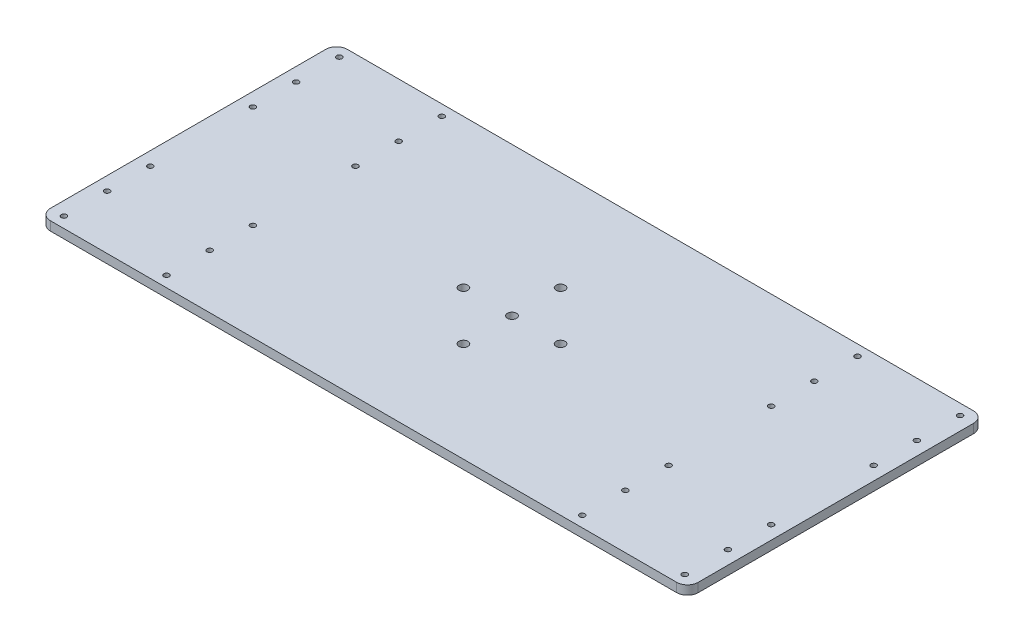
SolidWorks part; units mm, degrees
ref_plane "Front Plane" through (0, 0, 0) normal (0, 0, 1) x (1, 0, 0)
ref_plane "Top Plane" through (0, 0, 0) normal (0, 1, 0) x (1, 0, 0)
ref_plane "Right Plane" through (0, 0, 0) normal (1, 0, 0) x (0, 0, -1)
sketch "Sketch1" plane through (0, 0, 0) normal (0, 1, 0) x (1, 0, 0)
  line L0 (-172.5, 82.5) -> (-172.5, -82.5) construction
  line L1 (-174, -82.5) -> (174, -82.5)
  line L2 (-180, -76.5) -> (-180, 76.5)
  line L3 (-174, 82.5) -> (174, 82.5)
  line L4 (180, -76.5) -> (180, 76.5)
  line L5 (-180, -82.5) -> (180, 82.5) construction
  line L6 (-180, 82.5) -> (180, -82.5) construction
  line L7 (0, 0) -> (-30, -30) construction
  line L8 (0, 82.5) -> (0, -82.5) construction
  line L9 (-180, 0) -> (180, 0) construction
  line L10 (-9.5, -10) -> (9.5, -10) construction
  line L11 (-10, -9.5) -> (-10, 9.5) construction
  line L12 (-9.5, 10) -> (9.5, 10) construction
  line L13 (10, -9.5) -> (10, 9.5) construction
  line L14 (-10, -10) -> (10, 10) construction
  line L15 (-10, 10) -> (10, -10) construction
  circle A0 centre (-172.5, 76.5) radius 1.5
  circle A1 centre (-172.5, 52.5) radius 1.5
  circle A2 centre (-172.5, 28.5) radius 1.5
  circle A3 centre (-115.5, 76.5) radius 1.5
  circle A4 centre (-115.5, 52.5) radius 1.5
  circle A5 centre (-115.5, 28.5) radius 1.5
  circle A6 centre (115.5, 28.5) radius 1.5
  circle A7 centre (115.5, 52.5) radius 1.5
  circle A8 centre (115.5, 76.5) radius 1.5
  circle A9 centre (172.5, 28.5) radius 1.5
  circle A10 centre (172.5, 52.5) radius 1.5
  circle A11 centre (172.5, 76.5) radius 1.5
  circle A12 centre (172.5, -76.5) radius 1.5
  circle A13 centre (172.5, -52.5) radius 1.5
  circle A14 centre (172.5, -28.5) radius 1.5
  circle A15 centre (115.5, -76.5) radius 1.5
  circle A16 centre (115.5, -52.5) radius 1.5
  circle A17 centre (115.5, -28.5) radius 1.5
  circle A18 centre (-115.5, -28.5) radius 1.5
  circle A19 centre (-115.5, -52.5) radius 1.5
  circle A20 centre (-115.5, -76.5) radius 1.5
  circle A21 centre (-172.5, -28.5) radius 1.5
  circle A22 centre (-172.5, -52.5) radius 1.5
  circle A23 centre (-172.5, -76.5) radius 1.5
  arc A24 (9.5, 10) -> (10, 9.5) centre (9.5, 9.5) cw construction
  arc A25 (10, -9.5) -> (9.5, -10) centre (9.5, -9.5) cw construction
  arc A26 (-9.5, -10) -> (-10, -9.5) centre (-9.5, -9.5) cw construction
  arc A27 (-10, 9.5) -> (-9.5, 10) centre (-9.5, 9.5) cw construction
  circle A28 centre (0, 27) radius 2.5
  circle A29 centre (27, 0) radius 2.5
  circle A30 centre (0, -27) radius 2.5
  circle A31 centre (-27, 0) radius 2.5
  circle A32 centre (0, 0) radius 2.5
  circle A33 centre (-30, -30) radius 2.5 construction
  circle A34 centre (-30, 30) radius 2.5 construction
  circle A35 centre (30, 30) radius 2.5 construction
  circle A36 centre (30, -30) radius 2.5 construction
  arc A37 (174, 82.5) -> (180, 76.5) centre (174, 76.5) cw
  arc A38 (180, -76.5) -> (174, -82.5) centre (174, -76.5) cw
  arc A39 (-174, -82.5) -> (-180, -76.5) centre (-174, -76.5) cw
  arc A40 (-180, 76.5) -> (-174, 82.5) centre (-174, 76.5) cw
  point P0 (0, 0)
  point P59 (0, 0)
  point P88 (0, 0)
  point P98 (0, 0)
  dimension "D5" = 3
  dimension "D9" = 0.5
  dimension "D10" = 17
  dimension "D11" = 5
  dimension "D14" = 57
  dimension "D15" = 45
  dimension "D17" = 60
  dimension "D18" = 5
  dimension "D19" = 6
  dimension "D1" = 360
  dimension "D2" = 165
  dimension "D3" = 7.5
  dimension "D4" = 3
  dimension "D6" = 6
  dimension "D8" = 20
  dimension "D13" = 24
  dimension "D7" = 2
  dimension "D12" = 4
  dimension "D16" = 4
extrude "Boss-Extrude1" add sketch "Sketch1" along normal blind 5
